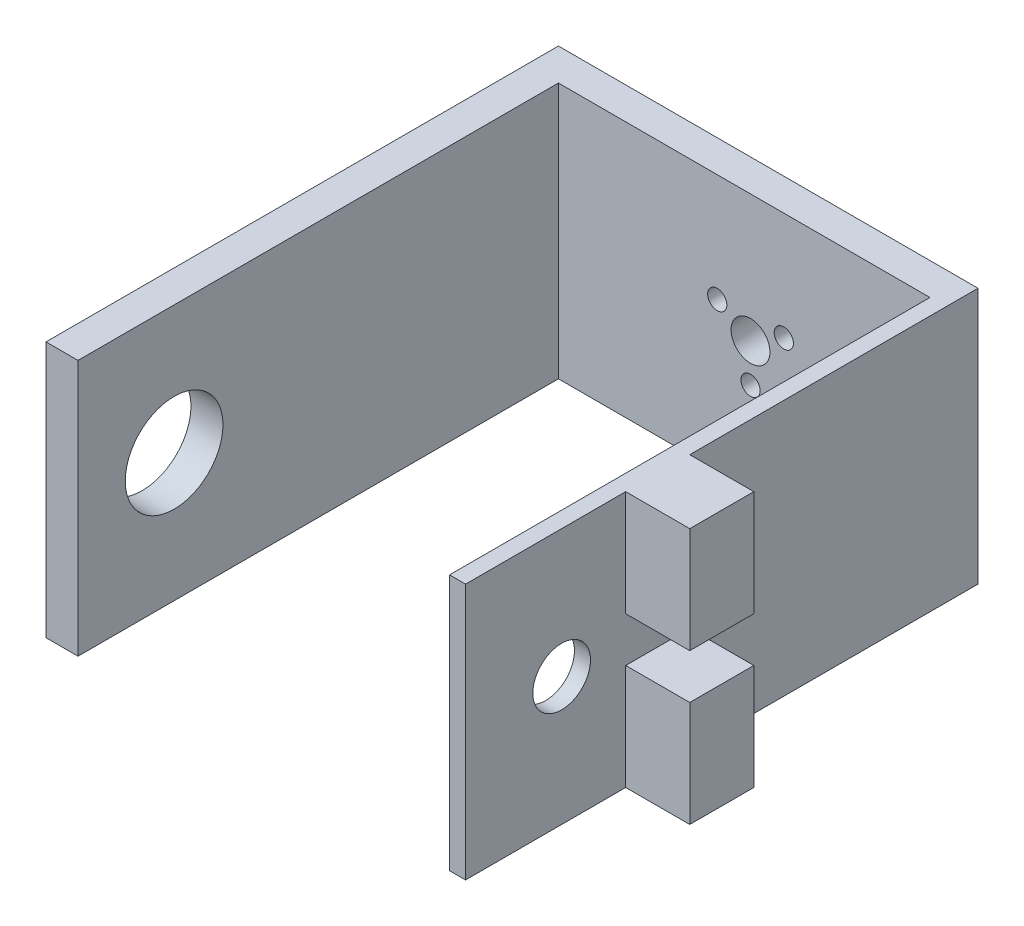
SolidWorks part; units mm, degrees
ref_plane "Front Plane" through (0, 0, 0) normal (0, 0, 1) x (1, 0, 0)
ref_plane "Top Plane" through (0, 0, 0) normal (0, 1, 0) x (1, 0, 0)
ref_plane "Right Plane" through (0, 0, 0) normal (1, 0, 0) x (0, 0, -1)
sketch "Sketch1" plane through (0, 0, 0) normal (0, 1, 0) x (1, 0, 0)
  line L0 (-991.4904, 0) -> (48583.0319, 0) construction
  line L1 (0, -991.4904) -> (0, 48583.0319) construction
  line L2 (-35, -42.2693) -> (-30, -42.2693)
  line L3 (-30, -42.2693) -> (-30, 32.7307)
  line L4 (-30, 32.7307) -> (28, 32.7307)
  line L5 (28, 32.7307) -> (28, -42.2693)
  line L6 (28, -42.2693) -> (30.5, -42.2693)
  line L7 (30.5, -42.2693) -> (30.5, 37.7307)
  line L8 (30.5, 37.7307) -> (-35, 37.7307)
  line L9 (-35, -42.2693) -> (-35, 37.7307)
  dimension "D1" = 2.5
  dimension "D2" = 5
  dimension "D3" = 80
  dimension "D4" = 30
  dimension "D5" = 5
  dimension "D6" = 28
extrude "Boss-Extrude1" add sketch "Sketch1" along normal blind 40
sketch "Sketch2" plane through (0, 0, -37.7307) normal (0, 0, -1) x (-1, 0, 0)
  line L0 (-1000, 20.1256) -> (49000, 20.1256) construction
  line L1 (0.0122, -980) -> (0.0122, 49020) construction
  line L2 (868.4066, -481.2422) -> (-42432.8636, 24518.7578) construction
  line L3 (-868.4328, -481.2713) -> (42432.8374, 24518.7287) construction
  line L4 (-30.5, 0) -> (35, 0)
  line L5 (35, 0) -> (35, 40)
  line L6 (35, 40) -> (-30.5, 40)
  line L7 (-30.5, 40) -> (-30.5, 0)
  line L8 (-30.5, 0) -> (35, 0)
  line L9 (35, 0) -> (35, 40)
  line L10 (35, 40) -> (-30.5, 40)
  line L11 (-30.5, 40) -> (-30.5, 0)
  circle A0 centre (0.0122, 20.1256) radius 10
  circle A1 centre (0.0122, 14.1256) radius 1.5
  circle A2 centre (-5.184, 23.1256) radius 1.5
  circle A3 centre (5.2083, 23.1256) radius 1.5
  circle A4 centre (0.0122, 20.1256) radius 3.035
  point P6 (2.25, 40)
  dimension "D3" = 20
  dimension "D5" = 3
  dimension "D8" = 120
  dimension "D10" = 6.07
  dimension "D2" = 20
  dimension "D4" = 6
  dimension "D6" = 6
  dimension "D7" = 6
  dimension "D9" = 120
  dimension "D1" = 0
extrude "Cut-Extrude1" cut sketch "Sketch2" against normal through all contours A3 | A1 | A2 region at (-0.0122, 14.1256, -37.7307) region at (5.184, 23.1256, -37.7307) region at (-5.2083, 23.1256, -37.7307)
sketch "Sketch3" plane through (-35, 0, 0) normal (-1, 0, 0) x (0, 0, 1)
  line L4 (-37.7307, 0) -> (42.2693, 0)
  line L5 (42.2693, 0) -> (42.2693, 40)
  line L6 (42.2693, 40) -> (-37.7307, 40)
  line L7 (-37.7307, 40) -> (-37.7307, 0)
  line L8 (-37.7307, 0) -> (42.2693, 0)
  line L9 (42.2693, 0) -> (42.2693, 40)
  line L10 (42.2693, 40) -> (-37.7307, 40)
  line L11 (-37.7307, 40) -> (-37.7307, 0)
  circle A0 centre (27.2693, 20) radius 7.625
  dimension "D3" = 15.25
  dimension "D2" = 65
  dimension "D1" = 0
extrude "Cut-Extrude2" cut sketch "Sketch3" against normal up to next contours A0 region at (-35, 20, 27.2693)
sketch "Sketch4" plane through (30.5, 0, 0) normal (1, 0, 0) x (0, 0, -1)
  line L0 (-17.2693, 23.5) -> (-7.2693, 23.5)
  line L1 (-7.2693, 0) -> (-17.2693, 0)
  line L2 (-7.2693, 0) -> (-7.2693, 40)
  line L3 (-7.2693, 40) -> (-17.2693, 40)
  line L4 (-42.2693, 0) -> (37.7307, 0)
  line L5 (37.7307, 0) -> (37.7307, 40)
  line L6 (37.7307, 40) -> (-42.2693, 40)
  line L7 (-42.2693, 40) -> (-42.2693, 0)
  line L8 (-42.2693, 0) -> (37.7307, 0)
  line L9 (37.7307, 0) -> (37.7307, 40)
  line L10 (37.7307, 40) -> (-42.2693, 40)
  line L11 (-42.2693, 40) -> (-42.2693, 0)
  line L12 (-17.2693, 0) -> (-17.2693, 40)
  line L13 (-7.2693, 0) -> (-17.2693, 40) construction
  line L14 (-7.2693, 40) -> (-17.2693, 0) construction
  line L15 (-17.2693, 16.5) -> (-7.2693, 16.5)
  line L16 (-17.2693, 20) -> (-7.2693, 20) construction
  circle A0 centre (-27.2693, 20) radius 7.625 construction
  circle A1 centre (-27.2693, 20) radius 7.625 construction
  circle A2 centre (-27.2693, 20) radius 4.5
  point P7 (-12.2693, 20)
  line M6 (-42.2693, 0) -> (37.7307, 0)
  line M8 (37.7307, 40) -> (-42.2693, 40)
  dimension "D3" = 9
  dimension "D2" = 10
  dimension "D4" = 10
  dimension "D5" = 7
  dimension "D1" = 0
extrude "Cut-Extrude4" cut sketch "Sketch4" against normal blind 10 contours A2 region at (30.5, 20, 27.2693)
extrude "Boss-Extrude2" add sketch "Sketch4<4>" along normal blind 10 contours L15 L12 L2 M6 | L12 L0 L2 M8 region at (30.5, 31.75, 12.2693) region at (30.5, 8.25, 12.2693)
sketch "Sketch4<4>" plane through (30.5, 0, 0) normal (1, 0, 0) x (0, 0, -1) same geometry as "Sketch4"
extrude "Cut-Extrude5" cut sketch "Sketch2<3>" against normal up to next contours A4 region at (-0.0122, 20.1256, -37.7307)
sketch "Sketch2<3>" plane through (0, 0, -37.7307) normal (0, 0, -1) x (-1, 0, 0) same geometry as "Sketch2"
